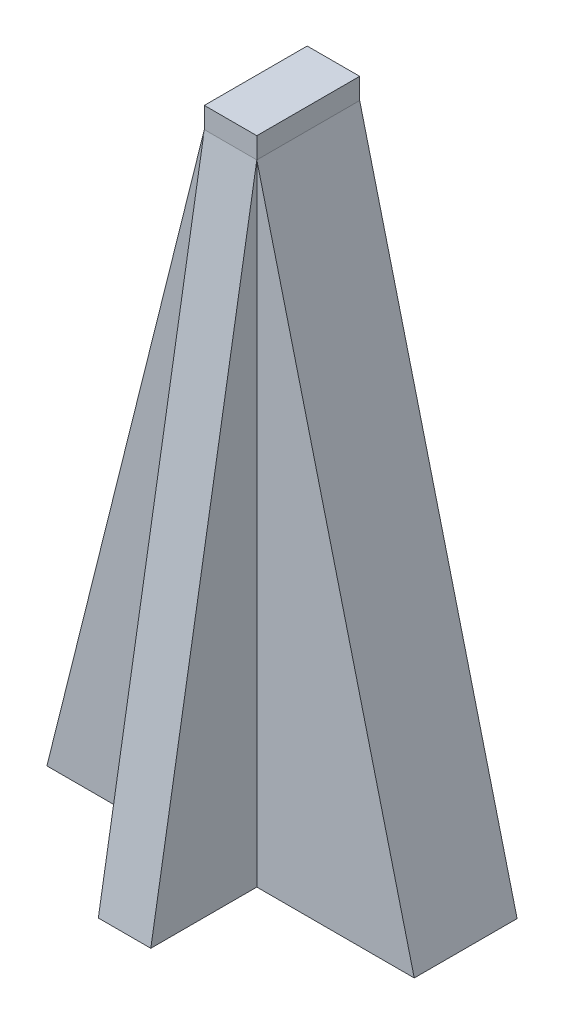
SolidWorks part; units mm, degrees
ref_plane "Front Plane" through (0, 0, 0) normal (0, 0, 1) x (1, 0, 0)
ref_plane "Top Plane" through (0, 0, 0) normal (0, 1, 0) x (1, 0, 0)
ref_plane "Right Plane" through (0, 0, 0) normal (1, 0, 0) x (0, 0, -1)
sketch "Sketch2" plane through (0, 0, 0) normal (0, 1, 0) x (1, 0, 0)
  line L1 (-6.35, -12.446) -> (6.35, -12.446)
  line L2 (-6.35, -12.446) -> (-6.35, 12.446)
  line L3 (-6.35, 12.446) -> (6.35, 12.446)
  line L4 (6.35, -12.446) -> (6.35, 12.446)
  line L5 (-6.35, -12.446) -> (6.35, 12.446) construction
  line L6 (-6.35, 12.446) -> (6.35, -12.446) construction
  point P0 (0, 0)
  dimension "D1" = 24.892
  dimension "D2" = 12.7
extrude "Boss-Extrude1" add sketch "Sketch2" along normal blind 5.08
sketch "Sketch3" plane through (0, 0, 0) normal (1, 0, 0) x (0, 0, -1)
  line L0 (-12.446, 0) -> (12.446, 0)
  line L2 (0, -152.4) -> (-38.1, -152.4)
  line L3 (-38.1, -152.4) -> (-12.446, 0)
  line L4 (0, -152.4) -> (38.1, -152.4)
  line L5 (38.1, -152.4) -> (12.446, 0)
  dimension "D1" = 38.1
  dimension "D2" = 38.1
extrude "Boss-Extrude2" add sketch "Sketch3" along normal mid plane 12.7 contours L3 L0 L5 L4 L2
sketch "Sketch4" plane through (0, 0, 0) normal (0, 0, 1) x (1, 0, 0)
  line L0 (-6.35, -152.4) -> (-44.45, -152.4)
  line L1 (-44.45, -152.4) -> (-6.35, 0)
  line L2 (-6.35, 0) -> (-6.35, -152.4)
  line L3 (0, -1000) -> (0, 49000) construction
  line L4 (44.45, -152.4) -> (6.35, 0)
  line L5 (6.35, -152.4) -> (44.45, -152.4)
  line L6 (6.35, 0) -> (6.35, -152.4)
  dimension "D1" = 38.1
extrude "Boss-Extrude3" add sketch "Sketch4" along normal mid plane 24.892 contours L1 L2 L0 | L4 L6 L5
shell "Shell1" thickness 5.08 removed face at (0, -152.4, 0)
